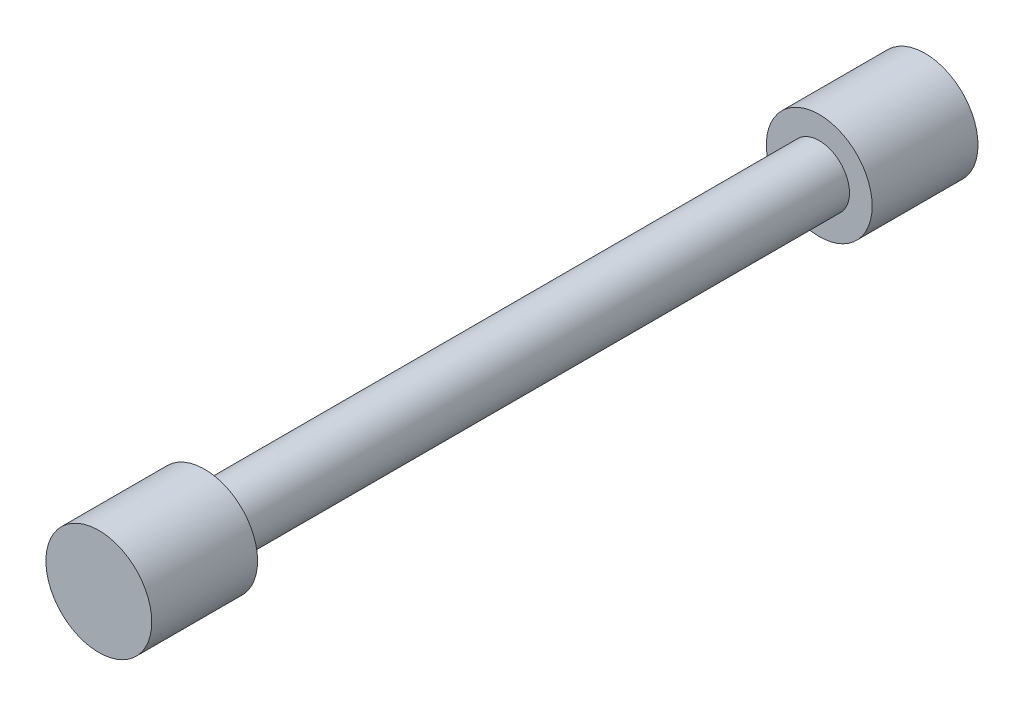
SolidWorks part; units mm, degrees
ref_plane "Front Plane" through (0, 0, 0) normal (0, 0, 1) x (1, 0, 0)
ref_plane "Top Plane" through (0, 0, 0) normal (0, 1, 0) x (1, 0, 0)
ref_plane "Right Plane" through (0, 0, 0) normal (1, 0, 0) x (0, 0, -1)
sketch "SK_Rod" plane through (0, 0, 0) normal (0, 1, 0) x (1, 0, 0)
  line L0 (0, -10) -> (0, 105.289) construction
  line L1 (0, -7) -> (7, -7)
  line L2 (7, -7) -> (7, 7)
  line L3 (7, 7) -> (4, 7)
  line L4 (4, 7) -> (4, 88.289)
  line L5 (4, 88.289) -> (7, 88.289)
  line L6 (7, 88.289) -> (7, 102.289)
  line L7 (7, 102.289) -> (0, 102.289)
  line L8 (0, 102.289) -> (0, -7)
  dimension "P1" = 10
  dimension "P2" = 105.289
  dimension "P3" = 7
  dimension "P4" = 7
  dimension "P5" = 7
  dimension "P6" = 7
  dimension "P7" = 7
  dimension "P8" = 4
  dimension "P9" = 7
  dimension "P10" = 4
  dimension "P11" = 88.289
  dimension "P12" = 7
  dimension "P13" = 88.289
  dimension "P14" = 7
  dimension "P15" = 102.289
  dimension "P16" = 102.289
revolve "Rod_Body" add sketch "SK_Rod" angle 360 about L0
sketch "SK_Ends" plane through (0, 0, 0) normal (0, 1, 0) x (1, 0, 0)
  point P0 (0, 0)
  point P2 (0, 95.289)
  dimension "P1" = 95.289
equation "\"Rod_length\" = 95.289"
